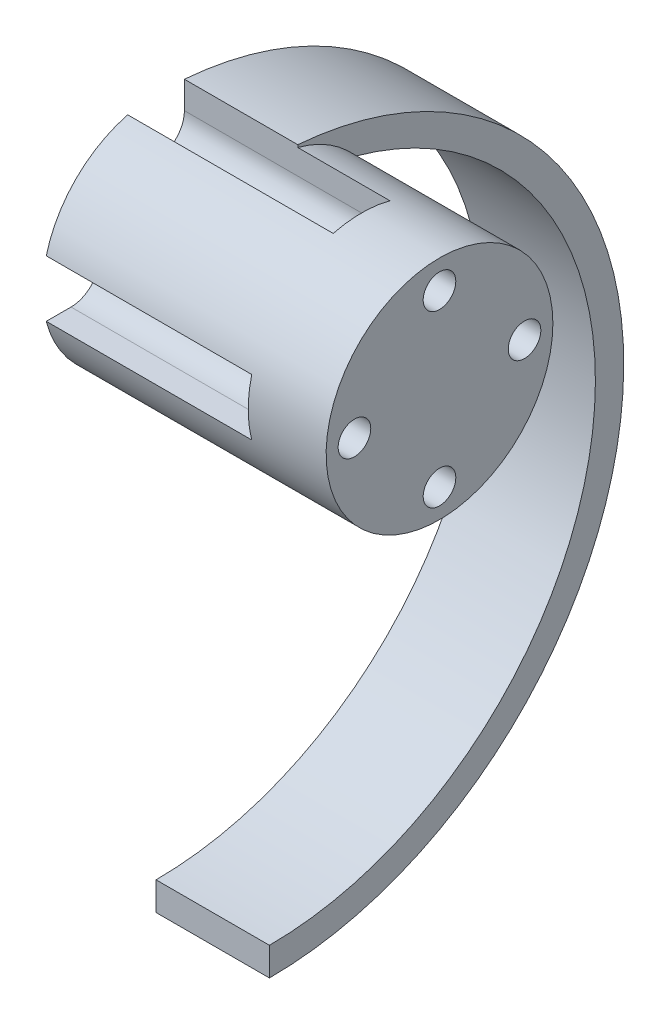
SolidWorks part; units mm, degrees
ref_plane "Front Plane" through (0, 0, 0) normal (0, 0, 1) x (1, 0, 0)
ref_plane "Top Plane" through (0, 0, 0) normal (0, 1, 0) x (1, 0, 0)
ref_plane "Right Plane" through (0, 0, 0) normal (1, 0, 0) x (0, 0, -1)
sketch "Hub-Sketch" plane through (0, 0, 0) normal (1, 0, 0) x (0, 0, -1)
  circle A0 centre (0, 0) radius 8
  circle A1 centre (0, 0) radius 6 construction
  circle A2 centre (0, 6) radius 1.15
  circle A3 centre (-6, 0) radius 1.15
  circle A4 centre (0, -6) radius 1.15
  circle A5 centre (6, 0) radius 1.15
  dimension "D1" = 16
  dimension "D2" = 12
  dimension "D3" = 2.3
extrude "Hub" add sketch "Hub-Sketch" against normal blind 12 and the other way blind 8
sketch "Leg-Sketch" plane through (8, 0, 0) normal (1, 0, 0) x (0, 0, -1)
  line L0 (0, -42) -> (0, -40)
  circle A1 centre (0, 0) radius 8 construction
  arc A2 (0, 8) -> (0, -42) centre (0, -17) cw
  arc A3 (6.0995, 5.1765) -> (0, -40) centre (0, -17) cw
  arc A4 (0, 8) -> (6.0995, 5.1765) centre (0, 0) cw
  dimension "D1" = 25
  dimension "D2" = 2
extrude "Leg" add sketch "Leg-Sketch" against normal up to surface (8 mm away) up to plane "Right Plane"
sketch "Clearance-Sketch" plane through (8, 0, 0) normal (1, 0, 0) x (0, 0, -1)
  line L8 (-2, 8) -> (2, 8)
  line L9 (2, 8) -> (2, 6)
  line L10 (-2, 6) -> (-2, 8)
  line L11 (8, 2) -> (8, -2)
  line L12 (8, -2) -> (6, -2)
  line L13 (6, 2) -> (8, 2)
  line L14 (2, -8) -> (-2, -8)
  line L15 (-2, -8) -> (-2, -6)
  line L16 (2, -6) -> (2, -8)
  line L17 (-8, -2) -> (-8, 2)
  line L18 (-8, 2) -> (-6, 2)
  line L19 (-6, -2) -> (-8, -2)
  arc A0 (6, -2) -> (6, 2) centre (6, 0) cw
  arc A3 (-2, -6) -> (2, -6) centre (0, -6) cw
  arc A10 (2, 6) -> (-2, 6) centre (0, 6) cw
  circle A11 centre (0, 6) radius 1.15 construction
  circle A12 centre (0, 0) radius 8 construction
  arc A13 (-6, 2) -> (-6, -2) centre (-6, 0) cw
  point P27 (0, 0)
  dimension "D1" = 2
extrude "Clearance" cut sketch "Clearance-Sketch" against normal offset from surface (14.5 mm away) 5.5
mirror "Mirror" about plane through (0, 0, 0) normal (1, 0, 0) of bodies 102
delete or keep bodies "KeepMirrorBody" type keep bodies bodies 104
equation "\"LEG_CLEARANCE\"= 3mm"
equation "\"LEG_WIDTH\"= 8mm"
equation "\"LEG_THICKNESS\"= 2mm"
equation "\"LEG_DIAMETER\"= 50mm"
equation "\"D1@Hub\"=\"HUB_WIDTH\""
equation "\"D2@Hub\"=\"LEG_WIDTH\""
equation "\"D2@Leg-Sketch\"=\"LEG_THICKNESS\""
equation "\"D1@Leg-Sketch\"=\"LEG_DIAMETER\"/2"
equation "\"HUB_WIDTH\"= \"LEG_CLEARANCE\" + \"LEG_WIDTH\" + 1mm"
